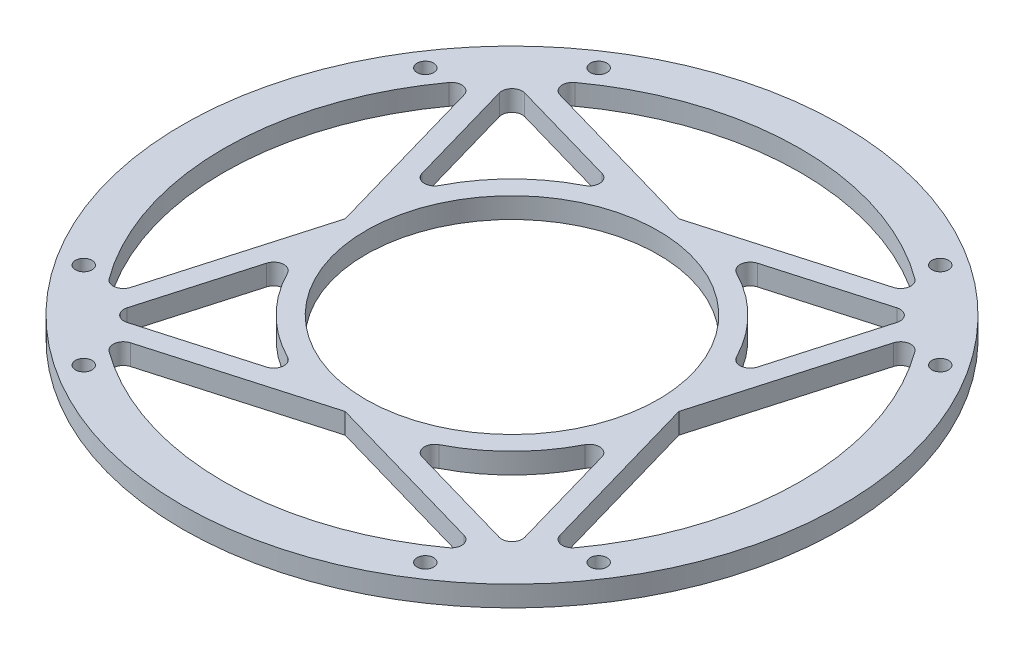
SolidWorks part; units mm, degrees
material "6061-T6 (SS)"
ref_plane "Front Plane" through (0, 0, 0) normal (0, 0, 1) x (1, 0, 0)
ref_plane "Top Plane" through (0, 0, 0) normal (0, 1, 0) x (1, 0, 0)
ref_plane "Right Plane" through (0, 0, 0) normal (1, 0, 0) x (0, 0, -1)
sketch "Sketch1" plane through (0, 0, 0) normal (0, 1, 0) x (1, 0, 0)
  circle A0 centre (0, 0) radius 54.61 construction
  circle A1 centre (0, 0) radius 101.6
  point P0 (0, 0)
  point P16 (-67.31, 0)
  point P18 (0, 76.2)
  dimension "D4" = 109.22
  dimension "D7" = 203.2
extrude "Boss-Extrude1" add sketch "Sketch1" along normal blind 6.35
ref_axis "Axis1" through (0, 0, 0) along (0, 1, 0)
sketch "Sketch4" plane through (0, 6.35, 0) normal (0, 1, 0) x (1, 0, 0)
  circle A0 centre (0, 0) radius 45.085
  dimension "D1" = 90.17
extrude "Cut-Extrude1" cut sketch "Sketch4" against normal through all
sketch "Sketch5" plane through (0, 6.35, 0) normal (0, 1, 0) x (1, 0, 0)
  line L0 (-67.8972, 57.3863) -> (-51.435, 0)
  line L1 (0, 0) -> (-153.6953, 0) construction
  line L2 (0, 0) -> (0, 145.3974) construction
  line L3 (-88.9, 0) -> (-51.435, 0)
  line L4 (0, 88.9) -> (0, 51.435)
  line L5 (-57.3863, 67.8972) -> (0, 51.435)
  line L8 (-15.1135, 49.1644) -> (-62.8618, 62.8618)
  line L10 (-62.8618, 62.8618) -> (-49.1644, 15.1135)
  arc A0 (-15.1135, 49.1644) -> (-49.1644, 15.1135) centre (0, 0) ccw
  arc A1 (0, 88.9) -> (-57.3863, 67.8972) centre (0, 0) ccw
  circle A2 centre (0, 0) radius 101.6 construction
  circle A3 centre (0, 0) radius 45.085 construction
  arc A4 (-67.8972, 57.3863) -> (-88.9, 0) centre (0, 0) ccw
  circle A5 centre (0, 0) radius 88.9 construction
  circle A6 centre (0, 0) radius 51.435 construction
  point P13 (0, 0)
  dimension "D1" = 12.7
  dimension "D2" = 6.35
  dimension "D3" = 6.35
  dimension "D5" = 6.35
  dimension "D4" = 90
extrude "Cut-Extrude2" cut sketch "Sketch5" against normal through all
hole_wizard "#10 Clearance Hole1" positions "Sketch8" profile "Sketch9" hole size "#10" standard "ANSI Inch" end condition through all
sketch "Sketch8" plane through (0, 6.35, 0) normal (0, 1, 0) x (1, 0, 0)
  point P0 (52.6514, 79.375)
  point P3 (79.375, 52.6514)
  point P6 (-52.6514, 79.375)
  point P9 (-79.375, 52.6514)
  point P12 (79.375, -52.6514)
  point P15 (52.6514, -79.375)
  point P18 (-52.6514, -79.375)
  point P21 (-79.375, -52.6514)
  point P25 (76.0355, -59.6172)
  point P27 (-80.1825, -57.7438)
  point P29 (-81.5368, 48.6372)
  point P30 (0, 0)
  point P31 (-79.375, 52.6514)
  point P33 (79.375, 52.6514)
sketch "Sketch9" plane through (52.6514, 6.35, -79.375) normal (1, 0, 0) x (0, 0, 1)
  line L0 (0, 0) -> (0, 6.35)
  line L1 (0, 6.35) -> (2.5527, 6.35)
  line L2 (2.5527, 6.35) -> (2.5527, 0)
  line L3 (2.5527, 0) -> (0, 0)
  line L4 (0, -6.35) -> (0, 107.95) construction
  dimension "Thru Hole Dia." = 5.1054
  dimension "Thru Hole Depth" = 6.35
fillet "Fillet1" radius 3.175 5 edges at (-57.3863, 3.175, -67.8972) (-49.1644, 3.175, -15.1135) (-15.1135, 3.175, -49.1644) (-62.8618, 3.175, -62.8618) (-67.8972, 3.175, -57.3863)
pattern_circular "CirPattern1" count 4 over 360 about axis through (0, 6.35, 0) along (0, -1, 0) of "Cut-Extrude2", "Fillet1"
